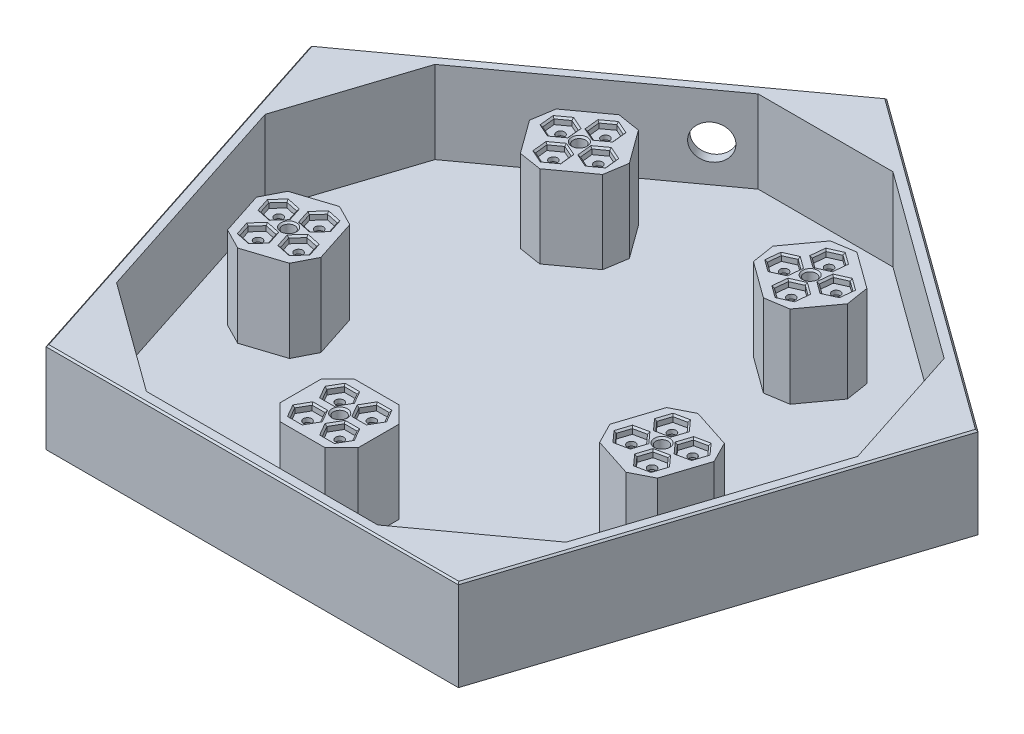
SolidWorks part; units mm, degrees
note: '?' marks a value the reader was unsure of.
ref_plane "Front Plane" through (0, 0, 0) normal (0, 0, 1) x (1, 0, 0)
ref_plane "Top Plane" through (0, 0, 0) normal (0, 1, 0) x (1, 0, 0)
ref_plane "Right Plane" through (0, 0, 0) normal (1, 0, 0) x (0, 0, -1)
sketch "Sketch1" plane through (0, 0, 0) normal (0, 1, 0) x (1, 0, 0)
  line L6 (102.7452, 33.3839) -> (0, 108.0327)
  line L7 (0, 108.0327) -> (-102.7452, 33.3839)
  line L8 (-102.7452, 33.3839) -> (-63.5, -87.4003)
  line L9 (-63.5, -87.4003) -> (63.5, -87.4003)
  line L10 (63.5, -87.4003) -> (102.7452, 33.3839)
  circle A0 centre (0, 0) radius 87.4003 construction
  circle A1 centre (0, 0) radius 7.429
  dimension "D1" = 127
extrude "Boss-Extrude1" add sketch "Sketch1" along normal blind 7.62
sketch "Sketch3" plane through (0, 7.62, 0) normal (0, 1, 0) x (1, 0, 0)
  line L1 (-1.0229, -55.499) -> (-2.9879, -52.0954)
  line L2 (-2.9879, -52.0954) -> (-6.9181, -52.0954)
  line L3 (-6.9181, -52.0954) -> (-8.8831, -55.499)
  line L4 (-8.8831, -55.499) -> (-6.9181, -58.9026)
  line L5 (-6.9181, -58.9026) -> (-2.9879, -58.9026)
  line L6 (-2.9879, -58.9026) -> (-1.0229, -55.499)
  line L7 (8.8831, -55.499) -> (6.9181, -52.0954)
  line L8 (6.9181, -52.0954) -> (2.9879, -52.0954)
  line L9 (2.9879, -52.0954) -> (1.0229, -55.499)
  line L10 (1.0229, -55.499) -> (2.9879, -58.9026)
  line L11 (2.9879, -58.9026) -> (6.9181, -58.9026)
  line L12 (6.9181, -58.9026) -> (8.8831, -55.499)
  line L13 (8.8831, -65.405) -> (6.9181, -62.0014)
  line L14 (6.9181, -62.0014) -> (2.9879, -62.0014)
  line L15 (2.9879, -62.0014) -> (1.0229, -65.405)
  line L16 (1.0229, -65.405) -> (2.9879, -68.8086)
  line L17 (2.9879, -68.8086) -> (6.9181, -68.8086)
  line L18 (6.9181, -68.8086) -> (8.8831, -65.405)
  line L19 (-1.0229, -65.405) -> (-2.9879, -62.0014)
  line L20 (-2.9879, -62.0014) -> (-6.9181, -62.0014)
  line L21 (-6.9181, -62.0014) -> (-8.8831, -65.405)
  line L22 (-8.8831, -65.405) -> (-6.9181, -68.8086)
  line L23 (-6.9181, -68.8086) -> (-2.9879, -68.8086)
  line L24 (-2.9879, -68.8086) -> (-1.0229, -65.405)
  circle A0 centre (0, -60.452) radius 1.905
  circle A1 centre (-4.953, -55.499) radius 3.4036 construction
  circle A2 centre (4.953, -55.499) radius 3.4036 construction
  circle A3 centre (4.953, -65.405) radius 3.4036 construction
  circle A4 centre (-4.953, -65.405) radius 3.4036 construction
  dimension "D15" = 3.81
  dimension "D2" = 6.8072
  dimension "D3" = 6.8072
  dimension "D4" = 6.8072
  dimension "D5" = 6.8072
  dimension "D6" = 9.906
  dimension "D7" = 9.906
  dimension "D8" = 9.906
  dimension "D9" = 9.906
  dimension "D10" = 0
  dimension "D11" = 0
  dimension "D12" = 4.953
  dimension "D14" = 4.953
  dimension "D13" = 60.452
  dimension "D16" = 0
extrude "Cut-Extrude1" cut sketch "Sketch3" against normal blind 7.112
chamfer "Chamfer2" distance 0.508 angle 45 25 edges at (0, 7.62, 62.357) (-4.953, 7.62, 58.9026) (-7.9006, 7.62, 57.2008) (-7.9006, 7.62, 53.7972) (-4.953, 7.62, 52.0954) (-2.0054, 7.62, 53.7972) (-2.0054, 7.62, 57.2008) (4.953, 7.62, 58.9026) (2.0054, 7.62, 57.2008) (2.0054, 7.62, 53.7972) (4.953, 7.62, 52.0954) (7.9006, 7.62, 53.7972) (7.9006, 7.62, 57.2008) (4.953, 7.62, 68.8086) (2.0054, 7.62, 67.1068) (2.0054, 7.62, 63.7032) (4.953, 7.62, 62.0014) (7.9006, 7.62, 63.7032) (7.9006, 7.62, 67.1068) (-4.953, 7.62, 68.8086) (-7.9006, 7.62, 67.1068) (-7.9006, 7.62, 63.7032) (-4.953, 7.62, 62.0014) (-2.0054, 7.62, 63.7032) (-2.0054, 7.62, 67.1068)
sketch "Sketch4" plane through (0, 7.62, 0) normal (0, 1, 0) x (1, 0, 0)
  circle A0 centre (4.953, -55.499) radius 2.54
  circle A1 centre (4.953, -65.405) radius 2.54
  circle A2 centre (-4.953, -65.405) radius 2.54
  circle A3 centre (-4.953, -55.499) radius 2.54
  circle A4 centre (0, -60.452) radius 1.905 construction
  circle A5 centre (0, -60.452) radius 1.905 construction
  circle A6 centre (0, -60.452) radius 1.905
  dimension "D6" = 4.953
  dimension "D7" = 5.08
  dimension "D8" = 5.08
  dimension "D9" = 5.08
  dimension "D10" = 5.08
  dimension "D1" = 9.906
  dimension "D2" = 9.906
  dimension "D3" = 9.906
  dimension "D4" = 9.906
  dimension "D5" = 4.953
extrude "Cut-Extrude2" cut sketch "Sketch4" against normal through all
pattern_circular "CirPattern2" count 5 over 360 about axis through (0, 0, 0) along (0, 1, 0) of "Cut-Extrude1", "Chamfer2", "Cut-Extrude2"
sketch "Sketch5" plane through (0, 7.62, 0) normal (0, 1, 0) x (1, 0, 0)
  line L1 (0, 108.0327) -> (-102.7452, 33.3839)
  line L2 (-102.7452, 33.3839) -> (-63.5, -87.4003)
  line L3 (-63.5, -87.4003) -> (63.5, -87.4003)
  line L4 (63.5, -87.4003) -> (102.7452, 33.3839)
  line L5 (102.7452, 33.3839) -> (0, 108.0327)
  circle A0 centre (0, 0) radius 87.4003 construction
extrude "Cut-Extrude3" cut sketch "Sketch5" against normal blind 5.08
chamfer "Chamfer3" distance 0.508 angle 45 131 edges at (0, 2.54, 62.357) (-2.0054, 2.54, 53.7972) (-4.953, 2.54, 52.0954) (-7.9006, 2.54, 53.7972) (-7.9006, 2.54, 57.2008) (-4.953, 2.54, 58.9026) (-2.0054, 2.54, 57.2008) (7.9006, 2.54, 63.7032) (4.953, 2.54, 62.0014) (2.0054, 2.54, 63.7032) (2.0054, 2.54, 67.1068) (4.953, 2.54, 68.8086) (7.9006, 2.54, 67.1068) (57.4933, 2.54, 20.5857) (-48.7228, 2.54, 24.1382) (-48.0151, 2.54, 20.8089) (-50.5445, 2.54, 18.5315) (-53.7815, 2.54, 19.5833) (-54.4891, 2.54, 22.9125) (-51.9598, 2.54, 25.1899) (-61.205, 2.54, 17.7781) (-60.4974, 2.54, 14.4489) (-63.0268, 2.54, 12.1715) (-66.2638, 2.54, 13.2232) (-66.9714, 2.54, 16.5524) (-64.4421, 2.54, 18.8299) (63.0268, 2.54, 12.1715) (60.4974, 2.54, 14.4489) (61.205, 2.54, 17.7781) (64.4421, 2.54, 18.8299) (66.9714, 2.54, 16.5524) (66.2638, 2.54, 13.2232) (50.5445, 2.54, 18.5315) (48.0151, 2.54, 20.8089) (48.7228, 2.54, 24.1382) (51.9598, 2.54, 25.1899) (54.4891, 2.54, 22.9125) (53.7815, 2.54, 19.5833) (25.2295, 2.54, -48.1667) (26.6138, 2.54, -45.0574) (29.9988, 2.54, -44.7016) (31.9994, 2.54, -47.4552) (30.615, 2.54, -50.5645) (27.2301, 2.54, -50.9203) (35.5328, 2.54, -47.0017) (-51.7839, 2.54, 14.717) (-51.0762, 2.54, 11.3878) (-53.6056, 2.54, 9.1103) (-56.8426, 2.54, 10.1621) (-57.5503, 2.54, 13.4913) (-55.0209, 2.54, 15.7688) (-43.8355, 2.54, -46.8931) (-40.4506, 2.54, -47.2489) (-39.0662, 2.54, -50.3582) (-41.0668, 2.54, -53.1118) (-44.4517, 2.54, -52.756) (-45.8361, 2.54, -49.6467) (-35.5328, 2.54, -47.0017) (-29.9988, 2.54, -44.7016) (-26.6138, 2.54, -45.0574) (-25.2295, 2.54, -48.1667) (-27.2301, 2.54, -50.9203) (-30.615, 2.54, -50.5645) (-31.9994, 2.54, -47.4552) (83.1226, 2.54, 27.0082) (0, 2.54, 87.4003) (-83.1226, 2.54, 27.0082) (-51.3726, 2.54, -70.7083) (51.3726, 2.54, -70.7083) (-38.0129, 2.54, -38.879) (-34.628, 2.54, -39.2348) (-33.2436, 2.54, -42.3441) (-35.2442, 2.54, -45.0977) (-38.6291, 2.54, -44.7419) (-40.0135, 2.54, -41.6326) (39.0662, 2.54, -50.3582) (40.4506, 2.54, -47.2489) (43.8355, 2.54, -46.8931) (45.8361, 2.54, -49.6467) (44.4517, 2.54, -52.756) (41.0668, 2.54, -53.1118) (-35.8214, 2.54, -52.7157) (-32.4364, 2.54, -53.0715) (-31.0521, 2.54, -56.1808) (-33.0527, 2.54, -58.9344) (-36.4376, 2.54, -58.5786) (-37.822, 2.54, -55.4693) (-57.4933, 2.54, 20.5857) (33.2436, 2.54, -42.3441) (34.628, 2.54, -39.2348) (38.0129, 2.54, -38.879) (40.0135, 2.54, -41.6326) (38.6291, 2.54, -44.7419) (35.2442, 2.54, -45.0977) (31.0521, 2.54, -56.1808) (32.4364, 2.54, -53.0715) (35.8214, 2.54, -52.7157) (37.822, 2.54, -55.4693) (36.4376, 2.54, -58.5786) (33.0527, 2.54, -58.9344) (53.6056, 2.54, 9.1103) (51.0762, 2.54, 11.3878) (51.7839, 2.54, 14.717) (55.0209, 2.54, 15.7688) (57.5503, 2.54, 13.4913) (56.8426, 2.54, 10.1621) (59.9656, 2.54, 21.5926) (57.4363, 2.54, 23.8701) (58.1439, 2.54, 27.1993) (61.3809, 2.54, 28.2511) (63.9103, 2.54, 25.9736) (63.2027, 2.54, 22.6444) (-58.1439, 2.54, 27.1993) (-57.4363, 2.54, 23.8701) (-59.9656, 2.54, 21.5926) (-63.2027, 2.54, 22.6444) (-63.9103, 2.54, 25.9736) (-61.3809, 2.54, 28.2511) (-2.0054, 2.54, 63.7032) (-4.953, 2.54, 62.0014) (-7.9006, 2.54, 63.7032) (-7.9006, 2.54, 67.1068) (-4.953, 2.54, 68.8086) (-2.0054, 2.54, 67.1068) (7.9006, 2.54, 53.7972) (4.953, 2.54, 52.0954) (2.0054, 2.54, 53.7972) (2.0054, 2.54, 57.2008) (4.953, 2.54, 58.9026) (7.9006, 2.54, 57.2008) (0, 2.54, 7.429)
sketch "Sketch6" plane through (0, 0, 0) normal (0, -1, 0) x (1, 0, 0)
  line L1 (-63.5, 87.4003) -> (-102.7452, -33.3839)
  line L2 (-102.7452, -33.3839) -> (0, -108.0327)
  line L3 (0, -108.0327) -> (102.7452, -33.3839)
  line L4 (102.7452, -33.3839) -> (63.5, 87.4003)
  line L5 (63.5, 87.4003) -> (-63.5, 87.4003)
  circle A0 centre (0, 0) radius 87.4003 construction
extrude "Boss-Extrude2" add sketch "Sketch6" along normal blind 25.4
sketch "Sketch7" plane through (0, 2.54, 0) normal (0, 1, 0) x (1, 0, 0)
  circle A0 centre (-35.5328, 48.9067) radius 1.905
  circle A1 centre (-34.437, 55.8251) radius 2.54
  circle A2 centre (-28.6144, 47.8109) radius 2.54
  circle A3 centre (-36.6286, 41.9883) radius 2.54
  circle A4 centre (-42.4512, 50.0025) radius 2.54
extrude "Cut-Extrude4" cut sketch "Sketch7" against normal through all
pattern_circular "CirPattern3" count 5 over 360 about axis through (0, 0, 0) along (0, 1, 0) of "Cut-Extrude4"
sketch "Sketch8" plane through (0, 2.54, 0) normal (0, 1, 0) x (1, 0, 0)
  line L0 (-32.5023, 40.1512) -> (-36.1564, 37.4964) construction
  line L1 (0, 60.6259) -> (-57.6587, 18.7344)
  line L2 (-57.6587, 18.7344) -> (-35.635, -49.0474)
  line L3 (-35.635, -49.0474) -> (35.635, -49.0474)
  line L4 (35.635, -49.0474) -> (57.6587, 18.7344)
  line L5 (57.6587, 18.7344) -> (0, 60.6259)
  circle A0 centre (0, 0) radius 49.0474 construction
  dimension "D1" = 2.54
extrude "Cut-Extrude5" cut sketch "Sketch8" against normal blind 25.4
sketch "Sketch10" plane through (0, 2.54, 0) normal (0, 1, 0) x (1, 0, 0)
  line L0 (-63.1309, -86.8923) -> (63.1309, -86.8923) construction
  line L1 (35.635, -49.0474) -> (12.0097, -49.0474)
  line L2 (35.635, -49.0474) -> (35.635, -84.3523)
  line L3 (35.635, -84.3523) -> (12.0097, -84.3523)
  line L4 (12.0097, -49.0474) -> (12.0097, -84.3523)
  line L6 (-35.635, -49.0474) -> (-12.0097, -49.0474)
  line L7 (-35.635, -49.0474) -> (-35.635, -84.3523)
  line L8 (-35.635, -84.3523) -> (-12.0097, -84.3523)
  line L9 (-12.0097, -49.0474) -> (-12.0097, -84.3523)
  dimension "D1" = 2.54
  dimension "D2" = 2.54
  dimension "D3" = 2.54
  dimension "D4" = 2.54
extrude "Cut-Extrude6" cut sketch "Sketch10" against normal up to surface (25.4 mm away) up to face at (0, -22.86, 0)
ref_axis "Axis2" through (0, 3.937, 0) along (0, -1, 0)?
pattern_circular "CirPattern4" count 5 over 360 about axis through (0, 0, 0) along (0, 1, 0) of "Cut-Extrude6"
sketch "Sketch12" plane through (0, 2.54, 0) normal (0, 1, 0) x (1, 0, 0)
  line L0 (35.635, -84.3523) -> (69.2119, -59.9572)
  line L1 (69.2119, -59.9572) -> (35.635, -49.0474)
  line L2 (35.635, -49.0474) -> (35.635, -84.3523)
  line L3 (12.0097, -49.0474) -> (12.0097, -84.3523) construction
  line L4 (-12.0097, -84.3523) -> (12.0097, -84.3523)
  line L5 (-12.0097, -84.3523) -> (-12.0097, -71.8566)
  line L6 (-12.0097, -71.8566) -> (12.0097, -71.8566)
  line L7 (12.0097, -84.3523) -> (12.0097, -71.8566)
  line L8 (-2.6946, -69.3166) -> (-7.2114, -69.3166) construction
  dimension "D1" = 2.54
extrude "Cut-Extrude7" cut sketch "Sketch12" against normal up to surface (25.4 mm away) up to face at (0, -22.86, 0)
pattern_circular "CirPattern5" count 5 over 360 about axis through (0, 0, 0) along (0, 1, 0) of "Cut-Extrude7"
chamfer "Chamfer5" distance 5.08 angle 45 20 edges at (32.5202, -10.16, -65.1924) (19.1133, -10.16, -46.7393) (51.9523, -10.16, -51.0741) (38.5454, -10.16, -32.621) (42.9356, -10.16, 26.5784) (64.6285, -10.16, 33.6268) (72.0509, -10.16, 10.783) (50.3581, -10.16, 3.7346) (-12.0097, -10.16, 49.0474) (12.0097, -10.16, 49.0474) (12.0097, -10.16, 71.8566) (-12.0097, -10.16, 71.8566) (-51.9523, -10.16, -51.0741) (-38.5454, -10.16, -32.621) (-32.5202, -10.16, -65.1924) (-19.1133, -10.16, -46.7393) (-50.3581, -10.16, 3.7346) (-42.9356, -10.16, 26.5784) (-64.6285, -10.16, 33.6268) (-72.0509, -10.16, 10.783)
sketch "Sketch13" plane through (-51.3726, 0, -70.7083) normal (-0.5878, 0, -0.809) x (-0.809, 0, 0.5878)
  line L0 (0, 3.937) -> (0, -26.797) construction
  circle A0 centre (-25.4, -11.4592) radius 5.33
  dimension "D2" = 10.66
  dimension "D1" = 25.4
extrude "Cut-Extrude8" cut sketch "Sketch13" against normal blind 7.62
sketch "Sketch14" plane through (0, 0.508, 0) normal (0, 1, 0) x (1, 0, 0)
  line L1 (-33.9649, 51.3331) -> (-30.3108, 53.9879)
  line L2 (-30.3108, 53.9879) -> (-30.7829, 58.4799)
  line L3 (-30.7829, 58.4799) -> (-34.9092, 60.317)
  line L4 (-34.9092, 60.317) -> (-38.5633, 57.6622)
  line L5 (-38.5633, 57.6622) -> (-38.0911, 53.1702)
  line L6 (-38.0911, 53.1702) -> (-33.9649, 51.3331)
  line L7 (-41.979, 45.5105) -> (-38.3249, 48.1653)
  line L8 (-38.3249, 48.1653) -> (-38.797, 52.6573)
  line L9 (-38.797, 52.6573) -> (-42.9233, 54.4944)
  line L10 (-42.9233, 54.4944) -> (-46.5774, 51.8396)
  line L11 (-46.5774, 51.8396) -> (-46.1053, 47.3476)
  line L12 (-46.1053, 47.3476) -> (-41.979, 45.5105)
  line L13 (-36.1564, 37.4964) -> (-32.5023, 40.1512)
  line L14 (-32.5023, 40.1512) -> (-32.9744, 44.6432)
  line L15 (-32.9744, 44.6432) -> (-37.1007, 46.4803)
  line L16 (-37.1007, 46.4803) -> (-40.7548, 43.8255)
  line L17 (-40.7548, 43.8255) -> (-40.2827, 39.3335)
  line L18 (-40.2827, 39.3335) -> (-36.1564, 37.4964)
  line L19 (-28.1423, 43.319) -> (-24.4882, 45.9738)
  line L20 (-24.4882, 45.9738) -> (-24.9603, 50.4658)
  line L21 (-24.9603, 50.4658) -> (-29.0866, 52.3029)
  line L22 (-29.0866, 52.3029) -> (-32.7407, 49.6481)
  line L23 (-32.7407, 49.6481) -> (-32.2685, 45.1561)
  line L24 (-32.2685, 45.1561) -> (-28.1423, 43.319)
  circle A0 centre (-34.437, 55.8251) radius 3.9116 construction
  circle A1 centre (-42.4512, 50.0025) radius 3.9116 construction
  circle A2 centre (-36.6286, 41.9883) radius 3.9116 construction
  circle A3 centre (-28.6144, 47.8109) radius 3.9116 construction
  circle A4 centre (-36.6286, 41.9883) radius 1.27
  circle A6 centre (-42.4512, 50.0025) radius 1.27
  circle A7 centre (-34.437, 55.8251) radius 1.27
  circle A8 centre (-28.6144, 47.8109) radius 1.27
  dimension "D1" = 2.54
  dimension "D2" = 2.54
  dimension "D3" = 2.54
  dimension "D4" = 2.54
extrude "Boss-Extrude4" add sketch "Sketch14" against normal blind 1.27
pattern_circular "CirPattern6" count 5 over 360 about axis through (0, 0, 0) along (0, 1, 0) of "Boss-Extrude4"
sketch "Sketch15" plane through (0, -25.4, 0) normal (0, -1, 0) x (1, 0, 0)
  circle A0 centre (-4.953, 65.405) radius 3.81
  circle A1 centre (4.953, 65.405) radius 3.81
  circle A2 centre (4.953, 55.499) radius 3.81
  circle A3 centre (-4.953, 55.499) radius 3.81
  dimension "D1" = 7.62
  dimension "D2" = 7.62
  dimension "D3" = 7.62
  dimension "D4" = 7.62
extrude "Cut-Extrude9" cut sketch "Sketch15" against normal up to surface (24.638 mm away) up to face at (-4.2065, -0.762, 64.3775)
pattern_circular "CirPattern7" count 5 over 360 about axis through (0, 0, 0) along (0, 1, 0) of "Cut-Extrude9"
equation "\"Standoff\"= 0.268"
equation "\"D2@Sketch3\"=\"Standoff\""
equation "\"D3@Sketch3\"=\"Standoff\""
equation "\"D4@Sketch3\"=\"Standoff\""
equation "\"D5@Sketch3\"=\"Standoff\""
